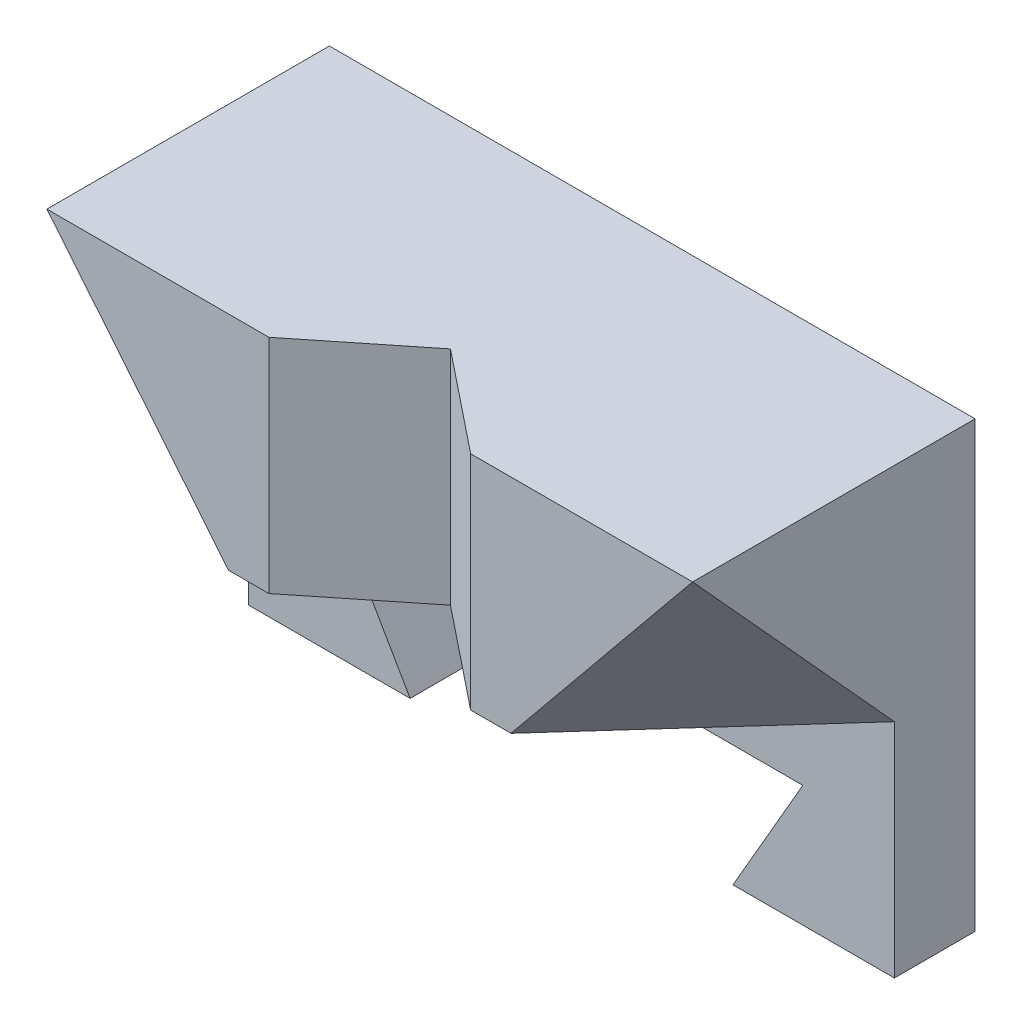
SolidWorks part; units mm, degrees
ref_plane "前视基准面" through (0, 0, 0) normal (0, 0, 1) x (1, 0, 0)
ref_plane "上视基准面" through (0, 0, 0) normal (0, 1, 0) x (1, 0, 0)
ref_plane "右视基准面" through (0, 0, 0) normal (1, 0, 0) x (0, 0, -1)
other "Configuration Table"
sketch "草图1" plane through (0, 0, 0) normal (0, 0, 1) x (1, 0, 0)
  line L1 (32, -22) -> (-32, -22)
  line L2 (32, -22) -> (32, 22)
  line L3 (32, 22) -> (-32, 22)
  line L4 (-32, -22) -> (-32, 22)
  line L5 (32, -22) -> (-32, 22) construction
  line L6 (32, 22) -> (-32, -22) construction
  point P0 (0, 0)
  dimension "D1" = 44
  dimension "D2" = 64
extrude "凸台-拉伸1" add sketch "草图1" against normal blind 8
sketch "草图2" plane through (0, 0, 0) normal (0, 0, 1) x (1, 0, 0)
  line L0 (0, 0) -> (-32, 0)
  line L1 (-32, 22) -> (-32, -22) construction
  line L2 (-32, 0) -> (-32, 22)
  line L3 (-32, 22) -> (32, 22)
  line L4 (32, 22) -> (32, 0)
  line L5 (32, -22) -> (32, 22) construction
  line L6 (32, 0) -> (0, 0)
extrude "凸台-拉伸2" add sketch "草图2" along normal blind 20
sketch "草图3" plane through (0, 0, 0) normal (0, 0, 1) x (1, 0, 0)
  line L0 (0, -22) -> (-16, -22)
  line L1 (-32, -22) -> (32, -22) construction
  line L2 (-16, -22) -> (-22.9282, -10)
  line L3 (-22.9282, -10) -> (22.9282, -10)
  line L4 (22.9282, -10) -> (16, -22)
  line L5 (16, -22) -> (0, -22)
  dimension "D1" = 12
  dimension "D2" = 16
  dimension "D3" = 16
  dimension "D4" = 60
  dimension "D5" = 60
extrude "切除-拉伸1" cut sketch "草图3" against normal blind 20
sketch "草图4" plane through (0, 0, 0) normal (0, -1, 0) x (1, 0, 0)
  line L0 (0, 20) -> (-10, 20)
  line L1 (-32, 20) -> (32, 20) construction
  line L2 (-10, 20) -> (0, 12)
  line L3 (0, 12) -> (10, 20)
  line L4 (10, 20) -> (0, 20)
  dimension "D1" = 10
  dimension "D2" = 10
  dimension "D3" = 8
extrude "切除-拉伸2" cut sketch "草图4" against normal blind 29
sketch "草图5" plane through (0, 0, 0) normal (0, -1, 0) x (1, 0, 0)
  line L0 (32, 20) -> (14, 20)
  line L1 (10, 20) -> (32, 20) construction
  line L2 (14, 20) -> (32, 0)
  line L3 (32, 0) -> (32, 20)
  line L4 (-32, 20) -> (-14, 20)
  line L5 (-32, 20) -> (-10, 20) construction
  line L6 (-14, 20) -> (-32, 0)
  line L7 (-32, 0) -> (-32, 20)
  dimension "D1" = 18
  dimension "D2" = 18
sketch "草图6" plane through (0, 0, 20) normal (0, 0, 1) x (1, 0, 0)
  line L0 (-14, 0) -> (-32, 22)
  line L1 (-32, 0) -> (-14, 0) construction
  line L2 (14, 0) -> (32, 22)
  line L3 (32, 0) -> (14, 0) construction
ref_plane "基准面1" through (-32, 0, 20) normal (-0.6332, 0.774, 0) x (0.774, 0.6332, 0)
sketch "草图7" plane through (-32, 0, 20) normal (-0.6332, 0.774, 0) x (0.774, 0.6332, 0)
  line L0 (0, 20) -> (13.9312, 0)
  line L1 (13.9312, 0) -> (0, 0)
  line L2 (0, 0) -> (0, 20)
extrude "切除-拉伸3" cut sketch "草图7" against normal blind 29 and the other way blind 29
ref_plane "基准面2" through (32, 0, 20) normal (0.6332, 0.774, 0) x (0.774, -0.6332, 0)
sketch "草图8" plane through (32, 0, 20) normal (0.6332, 0.774, 0) x (0.774, -0.6332, 0)
  line L0 (0, 20) -> (0, 0)
  line L1 (0, 0) -> (-13.9312, 0)
  line L2 (-13.9312, 0) -> (0, 20)
extrude "切除-拉伸4" cut sketch "草图8" against normal blind 29 and the other way blind 29
